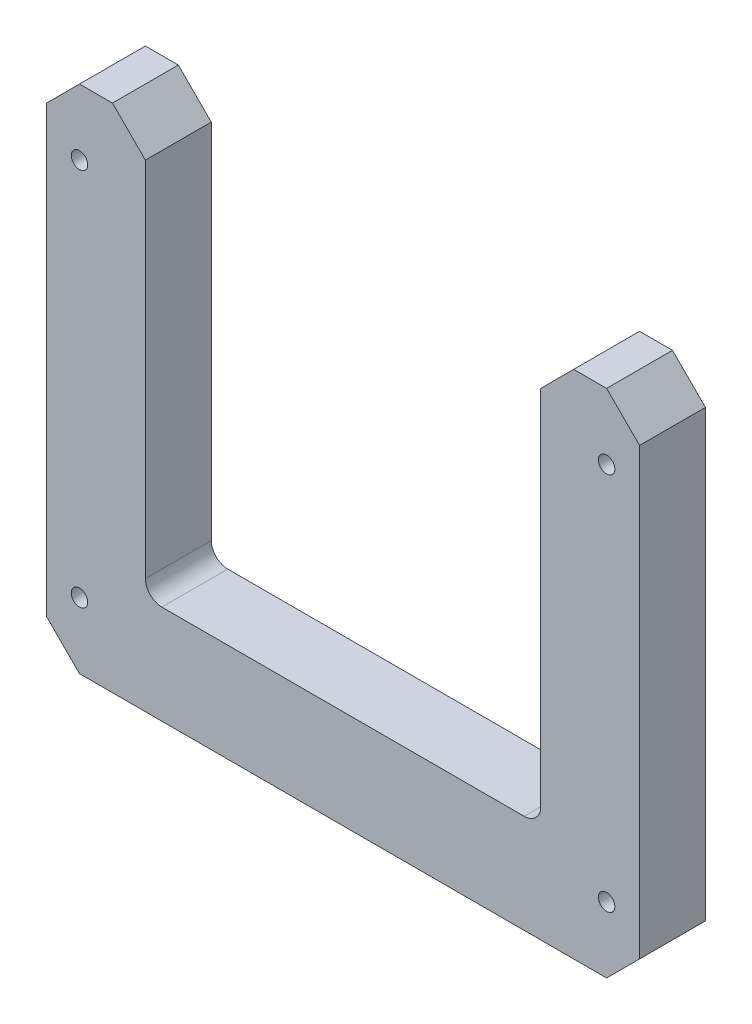
SolidWorks part; units mm, degrees
material "Beech"
ref_plane "Front Plane" through (0, 0, 0) normal (0, 0, 1) x (1, 0, 0)
ref_plane "Top Plane" through (0, 0, 0) normal (0, 1, 0) x (1, 0, 0)
ref_plane "Right Plane" through (0, 0, 0) normal (1, 0, 0) x (0, 0, -1)
sketch "Sketch1" plane through (0, 0, 0) normal (0, 0, 1) x (1, 0, 0)
  line L1 (-237.3775, 69.0432) -> (-237.3775, -16.6818) construction
  line L2 (-231.0275, 69.0432) -> (-231.0275, -10.3318)
  line L3 (-148.4775, 69.0432) -> (-148.4775, -16.6818) construction
  line L4 (-237.3775, -16.6818) -> (-148.4775, -16.6818) construction
  line L5 (-234.2025, -16.6818) -> (-151.6525, -16.6818) construction
  line L6 (-231.0275, -10.3318) -> (-154.8275, -10.3318)
  line L7 (-154.8275, 69.0432) -> (-154.8275, -10.3318)
  line L8 (-250.0775, 69.0432) -> (-250.0775, -29.3818)
  line L13 (-250.0775, -29.3818) -> (-135.7775, -29.3818)
  line L14 (-135.7775, 69.0432) -> (-135.7775, -29.3818)
  line L15 (-250.0775, 69.0432) -> (-231.0275, 69.0432)
  line L16 (-154.8275, 69.0432) -> (-135.7775, 69.0432)
  dimension "D1" = 6.35
  dimension "D2" = 12.7
extrude "Boss-Extrude1" add sketch "Sketch1" along normal blind 12.7
fillet "Fillet1" radius 3.175 2 edges at (-154.8275, -10.3318, 6.35) (-231.0275, -10.3318, 6.35)
chamfer "Chamfer1" distance 6.35 angle 45 6 edges at (-250.0775, -29.3818, 6.35) (-135.7775, -29.3818, 6.35) (-135.7775, 69.0432, 6.35) (-154.8275, 69.0432, 6.35) (-250.0775, 69.0432, 6.35) (-231.0275, 69.0432, 6.35)
hole_wizard "Hole1" positions "Sketch2" profile "Sketch3" legacy
sketch "Sketch2" plane through (-124.0045, -126.3871, -12.7) normal (0, 0, -1) x (-1, 0, 0)
  line L1 (0, 465.9538) -> (0, 66.1243) construction
  line L2 (126.073, 146.2179) -> (113.373, 146.2179) construction
  line L6 (119.723, 195.4304) -> (119.723, 97.0054) construction
  line L10 (68.923, 196.0654) -> (68.923, 112.2454) construction
  point P1 (113.65, 39.9076)
  point P3 (113.65, -64.959)
  point P5 (-94.6, 72.4743)
  point P7 (94.6, 72.4743)
  point P9 (0, 72.4743)
  point P11 (0, 104.2243)
  point P13 (0, 351.6538)
  point P15 (0, 213.0704)
  point P17 (40.9792, 213.0704)
  point P19 (166.7958, 213.0704)
  point P21 (207.775, 351.6538)
  point P23 (207.775, 244.1214)
  point P25 (207.775, 136.589)
  point P27 (207.775, 48.5243)
  point P29 (207.775, -78.4757)
  point P33 (-207.775, -78.4757)
  point P34 (-207.775, 48.5243)
  point P35 (-207.775, 136.589)
  point P36 (-207.775, 244.1214)
  point P37 (-207.775, 351.6538)
  point P38 (-166.7958, 213.0704)
  point P39 (-40.9792, 213.0704)
  point P40 (-113.65, -64.959)
  point P41 (-113.65, 39.9076)
  point P65 (119.723, 109.7054)
  point P68 (119.723, 182.7304)
  point P78 (18.123, 109.7054)
  point P79 (18.123, 182.7304)
  point P81 (0, 0)
  point P82 (113.65, 23.941)
  point P83 (0, 0)
  point P84 (207.775, -78.2752)
  point P85 (209.3058, -90.1558)
  point P86 (207.775, -78.4757)
  point P88 (113.65, -64.959)
  point P90 (207.775, 48.5243)
  point P92 (0, 0)
  point P93 (207.775, 136.589)
  point P95 (207.775, 244.1214)
  point P97 (207.775, 351.6538)
  point P99 (113.65, 39.9076)
  point P101 (94.6, 72.4743)
  point P103 (0, 72.4743)
  point P105 (0, 104.2243)
  point P107 (0, 0)
  point P108 (0, 213.0704)
  point P110 (0, 0)
  point P111 (0, 351.6538)
  point P113 (-40.9792, 213.0704)
  point P115 (-94.6, 72.4743)
  point P117 (-166.7958, 213.0704)
  point P119 (-113.65, -64.959)
  point P121 (0, 66.1243)
  point P124 (68.923, 112.2454)
sketch "Sketch3" plane through (-237.6545, -86.4795, -12.7) normal (1, 0, 0) x (0, 1, 0)
  line L0 (0, 0) -> (0, 32.7039)
  line L1 (0, 32.7039) -> (1.5875, 31.75)
  line L2 (1.5875, 31.75) -> (1.5875, 4.0177)
  line L3 (1.5875, 4.0177) -> (5.08, 0)
  line L4 (5.08, 0) -> (0, 0)
  line L5 (0, -14.3089) -> (0, 102.4216) construction
  line L6 (0, 32.7039) -> (-1.5875, 31.75) construction
  line L7 (-1.5875, 4.0177) -> (-5.08, 0) construction
  dimension "Diameter" = 3.175
  dimension "Depth" = 31.75
  dimension "C-Sink Diameter" = 10.16
  dimension "C-Sink Angle" = 82
  dimension "Drill Angle" = 118
